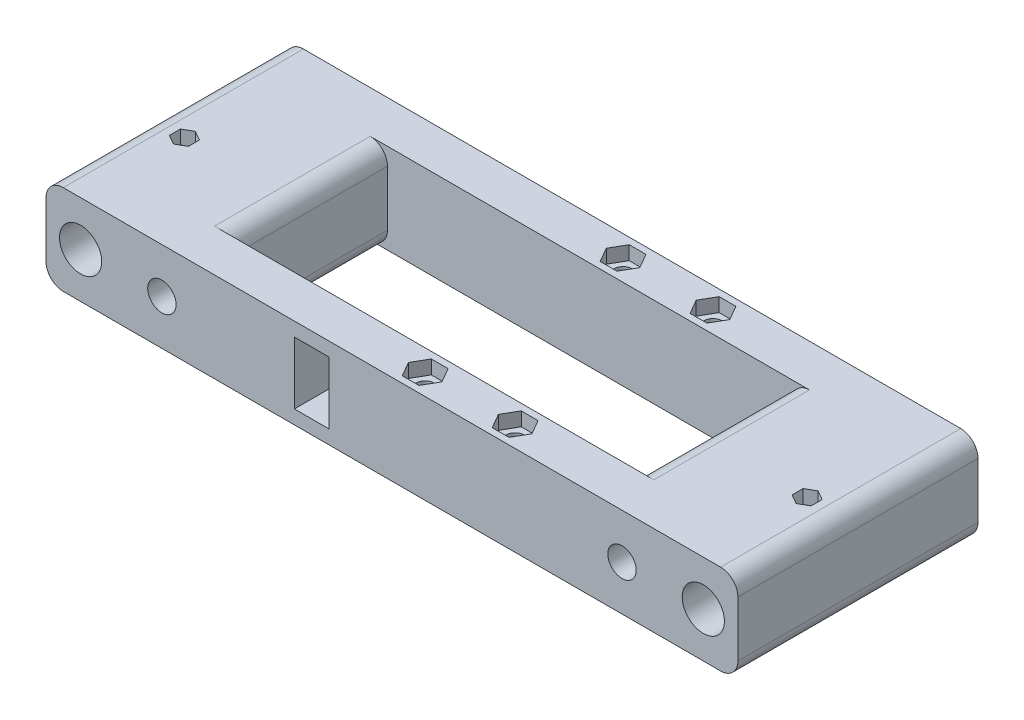
SolidWorks part; units mm, degrees
ref_plane "Front Plane" through (0, 0, 0) normal (0, 0, 1) x (1, 0, 0)
ref_plane "Top Plane" through (0, 0, 0) normal (0, 1, 0) x (1, 0, 0)
ref_plane "Right Plane" through (0, 0, 0) normal (1, 0, 0) x (0, 0, -1)
sketch "Sketch1" plane through (0, 0, 0) normal (0, 0, 1) x (1, 0, 0)
  line L0 (-58.5, 26) -> (-58.5, 0) construction
  line L1 (0, 0) -> (-100, 0)
  line L2 (0, 0) -> (0, 26)
  line L3 (0, 26) -> (-100, 26)
  line L4 (-100, 0) -> (-100, 26)
  circle A0 centre (-90, 13) radius 6.1
  circle A1 centre (-66.5, 13) radius 4.1
  point P9 (-100, 13)
  dimension "D3" = 12.2
  dimension "D4" = 8.2
  dimension "D1" = 100
  dimension "D2" = 26
  dimension "D5" = 23.5
  dimension "D6" = 10
  dimension "D7" = 8
  dimension "D8" = 41.5
extrude "Boss-Extrude1" add sketch "Sketch1" along normal blind 40
sketch "Sketch2" plane through (0, 0, 0) normal (0, 0, -1) x (-1, 0, 0)
  line L1 (100, 26) -> (0, 26)
  line L2 (100, 26) -> (100, 0)
  line L3 (100, 0) -> (0, 0)
  line L4 (0, 26) -> (0, 0)
extrude "Boss-Extrude2" add sketch "Sketch2" along normal blind 29.4
sketch "Sketch3" plane through (0, 26, 0) normal (0, 1, 0) x (1, 0, 0)
  line L0 (0, -40) -> (0, 29.4) construction
  line L1 (0, 17.2) -> (-58.5, 17.2)
  line L2 (0, 17.2) -> (0, -27.8)
  line L3 (0, -27.8) -> (-58.5, -27.8)
  line L4 (-58.5, 17.2) -> (-58.5, -27.8)
  line L5 (-100, -40) -> (-100, 29.4) construction
  line L6 (-100, 29.4) -> (0, 29.4) construction
  line L7 (0, -40) -> (-100, -40) construction
  dimension "D1" = 41.5
  dimension "D2" = 12.2
  dimension "D3" = 12.2
extrude "Cut-Extrude1" cut sketch "Sketch3" against normal up to next
mirror "Mirror2" about plane through (0, 0, 40) normal (-1, 0, 0) of "Boss-Extrude2", "Cut-Extrude1", "Boss-Extrude1"
sketch "Sketch4" plane through (0, 26, 0) normal (0, 1, 0) x (1, 0, 0)
  line L0 (-100, 29.4) -> (100, 29.4) construction
  line L1 (-5.5, 29.4) -> (-5.5, 17.2) construction
  line L2 (58.5, 17.2) -> (-58.5, 17.2) construction
  line L3 (58.5, 17.2) -> (58.5, -27.8) construction
  circle A0 centre (3.5, 23.3) radius 2.6
  circle A1 centre (29.5, 23.3) radius 2.6
  dimension "D1" = 6.1
  dimension "D3" = 9
  dimension "D4" = 26
  dimension "D5" = 5.2
  dimension "D2" = 64
extrude "Cut-Extrude2" cut sketch "Sketch4" against normal through all
sketch "Sketch5" plane through (0, 0, 0) normal (0, -1, 0) x (1, 0, 0)
  line L1 (34.2343, -23.3) -> (31.8671, -19.2)
  line L2 (31.8671, -19.2) -> (27.1329, -19.2)
  line L3 (27.1329, -19.2) -> (24.7657, -23.3)
  line L4 (24.7657, -23.3) -> (27.1329, -27.4)
  line L5 (27.1329, -27.4) -> (31.8671, -27.4)
  line L6 (31.8671, -27.4) -> (34.2343, -23.3)
  line L7 (-1.2343, -23.3) -> (1.1329, -27.4)
  line L8 (1.1329, -27.4) -> (5.8671, -27.4)
  line L9 (5.8671, -27.4) -> (8.2343, -23.3)
  line L10 (8.2343, -23.3) -> (5.8671, -19.2)
  line L11 (5.8671, -19.2) -> (1.1329, -19.2)
  line L12 (1.1329, -19.2) -> (-1.2343, -23.3)
  circle A0 centre (29.5, -23.3) radius 4.1 construction
  circle A1 centre (3.5, -23.3) radius 4.1 construction
  dimension "D1" = 8.2
  dimension "D2" = 8.2
extrude "Cut-Extrude3" cut sketch "Sketch5" against normal blind 4
ref_plane "Plane1" through (0, 0, 5.3) normal (0, 0, 1) x (1, 0, 0)
mirror "Mirror3" about plane through (0, 0, 5.3) normal (0, 0, 1) of "Cut-Extrude3", "Cut-Extrude2"
sketch "Sketch6" plane through (0, 0, 40) normal (0, 0, 1) x (1, 0, 0)
  line L0 (-8.1, 26) -> (-8.1, 0) construction
  line L1 (100, 26) -> (-100, 26) construction
  line L2 (-100, 0) -> (100, 0) construction
  line L3 (0.9, 26) -> (0.9, 4) construction
  line L4 (-100, 26) -> (-100, 0) construction
  line L5 (-18.2, 22) -> (-28.2, 22)
  line L6 (-18.2, 22) -> (-18.2, 4)
  line L7 (-18.2, 4) -> (-28.2, 4)
  line L8 (-28.2, 22) -> (-28.2, 4)
  point P12 (-28.2, 13)
  point P15 (-100, 13)
  dimension "D1" = 9
  dimension "D2" = 10.1
  dimension "D3" = 10
  dimension "D4" = 18
extrude "Cut-Extrude4" cut sketch "Sketch6" against normal up to vertex (14 mm away) up to point (0, -58.5, 26)
fillet "Fillet1" radius 5 8 edges at (58.5, 0, 5.3) (-58.5, 0, 5.3) (58.5, 26, 5.3) (100, 0, 5.3) (100, 26, 5.3) (-100, 0, 5.3) (-100, 26, 5.3) (-58.5, 26, 5.3)
sketch "Sketch7" plane through (0, 26, 0) normal (0, 1, 0) x (1, 0, 0)
  line L0 (63.5, 17.2) -> (-63.5, 17.2) construction
  line L1 (8.3497, 23.3) -> (5.9249, 27.5)
  line L2 (5.9249, 27.5) -> (1.0751, 27.5)
  line L3 (1.0751, 27.5) -> (-1.3497, 23.3)
  line L4 (-1.3497, 23.3) -> (1.0751, 19.1)
  line L5 (1.0751, 19.1) -> (5.9249, 19.1)
  line L6 (5.9249, 19.1) -> (8.3497, 23.3)
  line L7 (34.3497, 23.3) -> (31.9249, 27.5)
  line L8 (31.9249, 27.5) -> (27.0751, 27.5)
  line L9 (27.0751, 27.5) -> (24.6503, 23.3)
  line L10 (24.6503, 23.3) -> (27.0751, 19.1)
  line L11 (27.0751, 19.1) -> (31.9249, 19.1)
  line L12 (31.9249, 19.1) -> (34.3497, 23.3)
  circle A0 centre (3.5, 23.3) radius 4.2 construction
  circle A1 centre (29.5, 23.3) radius 4.2 construction
  point P20 (29.5, 19.1)
  dimension "D1" = 8.4
  dimension "D2" = 8.4
extrude "Cut-Extrude5" cut sketch "Sketch7" against normal blind 4
mirror "Mirror4" about plane through (0, 0, 5.3) normal (0, 0, 1) of "Cut-Extrude5"
sketch "Sketch8" plane through (0, 4, 0) normal (0, -1, 0) x (1, 0, 0)
  line L0 (27.1329, 38) -> (31.8671, 38) construction
  line L1 (31.8671, 38) -> (34.2343, 33.9) construction
  line L2 (34.2343, 33.9) -> (31.8671, 29.8) construction
  line L3 (31.8671, 29.8) -> (27.1329, 29.8) construction
  line L4 (27.1329, 29.8) -> (24.7657, 33.9) construction
  line L5 (24.7657, 33.9) -> (27.1329, 38) construction
  line L6 (1.1329, 38) -> (5.8671, 38) construction
  line L7 (5.8671, 38) -> (8.2343, 33.9) construction
  line L8 (8.2343, 33.9) -> (5.8671, 29.8) construction
  line L9 (5.8671, 29.8) -> (1.1329, 29.8) construction
  line L10 (1.1329, 29.8) -> (-1.2343, 33.9) construction
  line L11 (-1.2343, 33.9) -> (1.1329, 38) construction
  line L12 (27.1329, 38) -> (31.8671, 38)
  line L13 (31.8671, 38) -> (34.2343, 33.9)
  line L14 (34.2343, 33.9) -> (31.8671, 29.8)
  line L15 (31.8671, 29.8) -> (27.1329, 29.8)
  line L16 (27.1329, 29.8) -> (24.7657, 33.9)
  line L17 (24.7657, 33.9) -> (27.1329, 38)
  line L18 (1.1329, 38) -> (5.8671, 38)
  line L19 (5.8671, 38) -> (8.2343, 33.9)
  line L20 (8.2343, 33.9) -> (5.8671, 29.8)
  line L21 (5.8671, 29.8) -> (1.1329, 29.8)
  line L22 (1.1329, 29.8) -> (-1.2343, 33.9)
  line L23 (-1.2343, 33.9) -> (1.1329, 38)
  circle A0 centre (3.5, 33.9) radius 2.6 construction
  circle A1 centre (29.5, 33.9) radius 2.6 construction
  circle A2 centre (3.5, 33.9) radius 2.6
  circle A3 centre (29.5, 33.9) radius 2.6
extrude "Boss-Extrude3" add sketch "Sketch8" along normal up to surface (4 mm away) up to face at (3.5, 0, 33.9)
sketch "Sketch9" plane through (0, 4, 0) normal (0, -1, 0) x (1, 0, 0)
  line L0 (31.8671, -19.2) -> (27.1329, -19.2) construction
  line L1 (34.2343, -23.3) -> (31.8671, -19.2) construction
  line L2 (31.8671, -27.4) -> (34.2343, -23.3) construction
  line L3 (27.1329, -27.4) -> (31.8671, -27.4) construction
  line L4 (24.7657, -23.3) -> (27.1329, -27.4) construction
  line L5 (27.1329, -19.2) -> (24.7657, -23.3) construction
  line L6 (1.1329, -19.2) -> (-1.2343, -23.3) construction
  line L7 (5.8671, -19.2) -> (1.1329, -19.2) construction
  line L8 (8.2343, -23.3) -> (5.8671, -19.2) construction
  line L9 (5.8671, -27.4) -> (8.2343, -23.3) construction
  line L10 (1.1329, -27.4) -> (5.8671, -27.4) construction
  line L11 (-1.2343, -23.3) -> (1.1329, -27.4) construction
  line L12 (31.8671, -19.2) -> (27.1329, -19.2)
  line L13 (34.2343, -23.3) -> (31.8671, -19.2)
  line L14 (31.8671, -27.4) -> (34.2343, -23.3)
  line L15 (27.1329, -27.4) -> (31.8671, -27.4)
  line L16 (24.7657, -23.3) -> (27.1329, -27.4)
  line L17 (27.1329, -19.2) -> (24.7657, -23.3)
  line L18 (1.1329, -19.2) -> (-1.2343, -23.3)
  line L19 (5.8671, -19.2) -> (1.1329, -19.2)
  line L20 (8.2343, -23.3) -> (5.8671, -19.2)
  line L21 (5.8671, -27.4) -> (8.2343, -23.3)
  line L22 (1.1329, -27.4) -> (5.8671, -27.4)
  line L23 (-1.2343, -23.3) -> (1.1329, -27.4)
  circle A0 centre (3.5, -23.3) radius 2.6 construction
  circle A1 centre (29.5, -23.3) radius 2.6 construction
  circle A2 centre (3.5, -23.3) radius 2.6
  circle A3 centre (29.5, -23.3) radius 2.6
extrude "Boss-Extrude4" add sketch "Sketch9" along normal up to surface (4 mm away) up to face at (29.5, 0, -23.3)
sketch "Sketch10" plane through (0, 0, 0) normal (0, -1, 0) x (1, 0, 0)
  line L1 (-96.1, 0) -> (-83.9, 0) construction
  line L2 (83.9, 0) -> (96.1, 0) construction
  circle A0 centre (-90, 10) radius 1.5
  circle A1 centre (90, 10) radius 1.5
  point P5 (-90, 0)
  point P14 (90, 0)
  dimension "D3" = 3
  dimension "D4" = 3
  dimension "D1" = 10
  dimension "D2" = 10
extrude "Cut-Extrude6" cut sketch "Sketch10" against normal through all
sketch "Sketch11" plane through (0, 26, 0) normal (0, 1, 0) x (1, 0, 0)
  line L0 (-95, 29.4) -> (-95, -40) construction
  line L1 (-90, -13.1754) -> (-87.25, -11.5877)
  line L2 (-87.25, -11.5877) -> (-87.25, -8.4123)
  line L3 (-87.25, -8.4123) -> (-90, -6.8246)
  line L4 (-90, -6.8246) -> (-92.75, -8.4123)
  line L5 (-92.75, -8.4123) -> (-92.75, -11.5877)
  line L6 (-92.75, -11.5877) -> (-90, -13.1754)
  line L7 (90, -13.1754) -> (92.75, -11.5877)
  line L8 (92.75, -11.5877) -> (92.75, -8.4123)
  line L9 (92.75, -8.4123) -> (90, -6.8246)
  line L10 (90, -6.8246) -> (87.25, -8.4123)
  line L11 (87.25, -8.4123) -> (87.25, -11.5877)
  line L12 (87.25, -11.5877) -> (90, -13.1754)
  line L13 (95, -40) -> (95, 29.4) construction
  circle A0 centre (-90, -10) radius 2.75 construction
  circle A1 centre (90, -10) radius 2.75 construction
  point P10 (92.75, -10)
  dimension "D1" = 5.5
  dimension "D2" = 5.5
extrude "Cut-Extrude7" cut sketch "Sketch11" against normal blind 4
